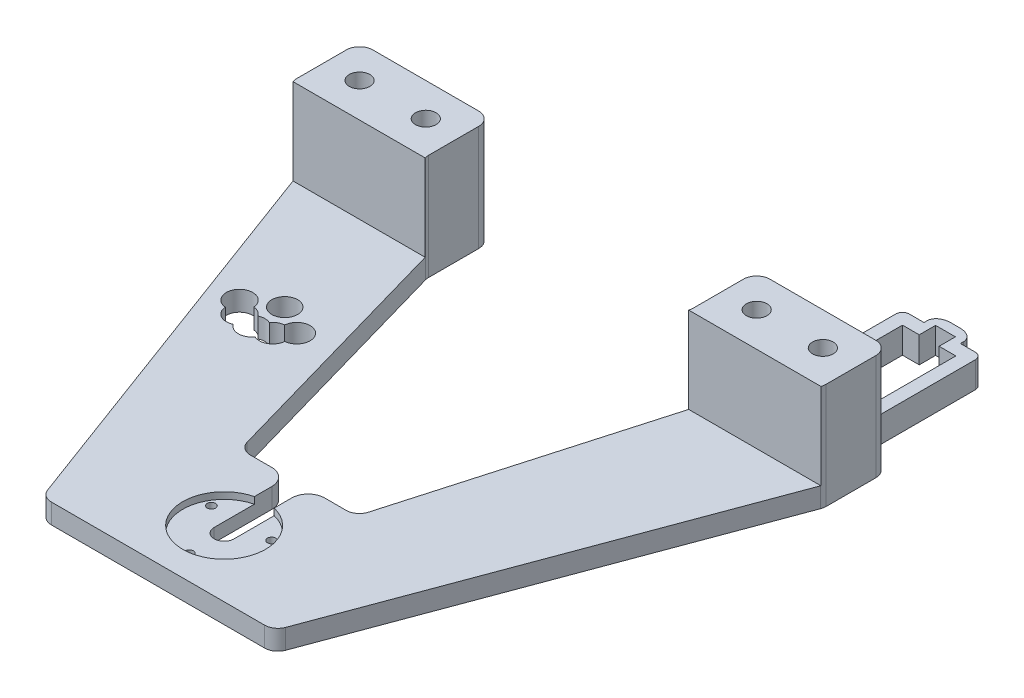
SolidWorks part; units mm, degrees
ref_plane "Front Plane" through (0, 0, 0) normal (0, 0, 1) x (1, 0, 0)
ref_plane "Top Plane" through (0, 0, 0) normal (0, 1, 0) x (1, 0, 0)
ref_plane "Right Plane" through (0, 0, 0) normal (1, 0, 0) x (0, 0, -1)
sketch "Sketch1" plane through (0, 0, 0) normal (0, 1, 0) x (1, 0, 0)
  line L0 (-96.52, 178.9428) -> (-55.88, 178.9428)
  line L1 (-50.8, 173.8628) -> (-50.8, 154.6109)
  line L3 (-101.6, 154.8128) -> (-101.6, 173.8628)
  line L4 (0, 53.8) -> (-18.3922, 53.8)
  line L6 (-40.9175, 0) -> (0, 0)
  line L8 (-101.2823, 153.0443) -> (-45.6797, 3.3116)
  line L9 (0, 53.8) -> (0, 0)
  line L10 (-23.2771, 57.4855) -> (-50.6049, 153.2164)
  circle A0 centre (-88.9, 166.2428) radius 3.9687
  circle A1 centre (-63.5, 166.2428) radius 3.9688
  arc A2 (-55.88, 178.9428) -> (-50.8, 173.8628) centre (-55.88, 173.8628) cw
  arc A3 (-96.52, 178.9428) -> (-101.6, 173.8628) centre (-96.52, 173.8628) ccw
  arc A4 (-101.2823, 153.0443) -> (-101.6, 154.8128) centre (-96.52, 154.8128) cw
  arc A5 (-45.6797, 3.3116) -> (-40.9175, 0) centre (-40.9175, 5.08) ccw
  arc A6 (-18.3922, 53.8) -> (-23.2771, 57.4855) centre (-18.3922, 58.88) cw
  arc A7 (-50.8, 154.6109) -> (-50.6049, 153.2164) centre (-45.72, 154.6109) ccw
  point P18 (-50.8, 178.9428)
  point P21 (-101.6, 178.9428)
  point P47 (0, 26.9)
  point P51 (-101.6, 153.9)
  point P54 (-44.45, 0)
  point P57 (-22.225, 53.8)
  point P60 (-50.8, 153.9)
  dimension "D3" = 7.9375
  dimension "D6" = 5.08
  dimension "D13" = 5.08
  dimension "D14" = 5.08
  dimension "D15" = 5.08
  dimension "D16" = 5.08
  dimension "D1" = 50.8
  dimension "D2" = 19.05
  dimension "D4" = 12.7
  dimension "D5" = 12.7
  dimension "D7" = 101.6
  dimension "D8" = 127
  dimension "D9" = 12.7
  dimension "D10" = 44.45
  dimension "D11" = 22.225
  dimension "D12" = 53.8
extrude "Boss-Extrude2" add sketch "Sketch1" along normal blind 40.64
mirror "Mirror1" about plane through (0, 40.64, -53.8) normal (-1, 0, 0) of "Boss-Extrude2"
sketch "Sketch4" plane through (0, 40.64, 0) normal (0, 1, 0) x (1, 0, 0)
  line L2 (18.3922, 53.8) -> (-18.3922, 53.8) construction
  circle A0 centre (11.5484, 32.0195) radius 1.5875
  circle A1 centre (0, 12.017) radius 1.5875
  circle A2 centre (-11.5484, 32.0195) radius 1.5875
  point P9 (0, 25.352)
  dimension "D1" = 3.175
  dimension "D3" = 28.448
  dimension "D4" = 13.335
  dimension "D2" = 3
extrude "Cut-Extrude1" cut sketch "Sketch4" against normal through all
sketch "Sketch5" plane through (0, 0, 0) normal (0, 1, 0) x (1, 0, 0)
  line L0 (18.3922, 53.8) -> (-18.3922, 53.8) construction
  circle A0 centre (0, 25.352) radius 15.875
  dimension "D2" = 31.75
  dimension "D1" = 28.448
extrude "Cut-Extrude2" cut sketch "Sketch5" along normal blind 5.08 from offset 5.08
sketch "Sketch7" plane through (0, 40.64, 0) normal (0, 1, 0) x (1, 0, 0)
  line L1 (-155.1296, 153.0819) -> (166.308, 153.0819)
  line L2 (-155.1296, 153.0819) -> (-155.1296, 0)
  line L3 (-155.1296, 0) -> (166.308, 0)
  line L4 (166.308, 153.0819) -> (166.308, 0)
  line L5 (-40.9175, 0) -> (40.9175, 0) construction
extrude "Cut-Extrude3" cut sketch "Sketch7" against normal offset from surface (33.02 mm away) 33.02 up to face at (11.5484, 40.64, -30.432)
sketch "Sketch8" plane through (0, 0, 0) normal (0, 1, 0) x (1, 0, 0)
  line L0 (0, 25.352) -> (0, 53.8) construction
  line L1 (18.3922, 53.8) -> (-18.3922, 53.8) construction
  line L2 (-3.81, 25.352) -> (-3.81, 53.8)
  line L3 (3.81, 25.352) -> (3.81, 53.8)
  arc A0 (-3.81, 25.352) -> (3.81, 25.352) centre (0, 25.352) ccw
  arc A1 (3.81, 53.8) -> (-3.81, 53.8) centre (0, 53.8) ccw
  point P5 (0, 39.576)
  dimension "D1" = 7.62
extrude "Cut-Extrude5" cut sketch "Sketch8" along direction (0, 1, 0) on the side of the normal through all
fillet "Fillet1" radius 6.35 1 edges at (-3.81, 3.81, -53.8) type face fillet first side face at (-11.1011, 3.81, -53.8) second side face at (-3.81, 4.2333, -39.9717)
fillet "Fillet2" radius 6.35 1 edges at (3.81, 3.81, -53.8) type face fillet first side face at (11.1011, 3.81, -53.8) second side face at (3.81, 4.2333, -39.9717)
sketch "Sketch9" plane through (0, 0, 0) normal (0, 1, 0) x (1, 0, 0)
  line L0 (-63.5, 166.2428) -> (-63.5, 178.9428) construction
  line L2 (-88.9, 166.2428) -> (-88.9, 178.9428) construction
  line L3 (-88.9, 166.2428) -> (-63.5, 166.2428) construction
  line L4 (-91.44, 173.9428) -> (-91.44, 224.7428)
  line L5 (-91.44, 224.7428) -> (-60.96, 224.7428)
  line L6 (-60.96, 224.7428) -> (-60.96, 173.9428)
  line L7 (-60.96, 173.9428) -> (-91.44, 173.9428)
  line L8 (-55.88, 178.9428) -> (-96.52, 178.9428) construction
  point P13 (-76.2, 173.9428)
  point P14 (-76.2, 166.2428)
  dimension "D1" = 30.48
  dimension "D2" = 50.8
  dimension "D3" = 5
extrude "Extrude-Thin1" add sketch "Sketch9" along normal blind 10 thin thin type one direction reverse wall 5
sketch "Sketch14" plane through (0, 0, 0) normal (0, -1, 0) x (1, 0, 0)
  line L0 (-65.96, -178.9428) -> (-86.44, -178.9428) construction
  line L1 (-81.2, -174.9428) -> (-71.2, -174.9428) construction
  line L2 (-76.2, -178.9428) -> (-76.2, -173.6531) construction
  circle A0 centre (-81.2, -174.9428) radius 1.95
  circle A1 centre (-71.2, -174.9428) radius 1.95
  point P6 (-76.2, -174.9428)
  dimension "D1" = 3.9
  dimension "D4" = 3.9
  dimension "D2" = 4
  dimension "D3" = 10
extrude "Cut-Extrude6" cut sketch "Sketch14" against normal blind 20
ref_plane "Plane2" through (-60.96, 10, -178.9428) normal (-1, 0, 0) x (0, 0, 1)
ref_plane "Plane3" through (-76.2, 0, 0) normal (1, 0, 0) x (0, 0, -1)
sketch "Sketch18" plane through (-60.96, 10, -178.9428) normal (-1, 0, 0) x (0, 0, 1)
  line L0 (-1.27, 0) -> (0, 1.524)
  line L1 (-45.8, 0) -> (0, 0) construction
  line L2 (0, 30.64) -> (0, -10) construction
  line L3 (0, 1.524) -> (0, 0)
  line L4 (0, 0) -> (-1.27, 0)
  dimension "D1" = 1.524
  dimension "D2" = 1.27
extrude "Boss-Extrude4" add sketch "Sketch18" along normal up to vertex (5 mm away) up to point (-65.96, 10, -178.9428)
mirror "Mirror3" about plane through (-76.2, 0, 0) normal (1, 0, 0) of "Boss-Extrude4"
mirror "Mirror5" about plane through (0, 0, 0) normal (1, 0, 0) of "Mirror3", "Boss-Extrude4", "Cut-Extrude6", "Extrude-Thin1"
fillet "Fillet3" radius 2.54 4 edges at (-91.44, 5, -224.7428) (-60.96, 5, -224.7428) (60.96, 5, -224.7428) (91.44, 5, -224.7428)
sketch "Sketch19" plane through (0, 0, -224.7428) normal (0, 0, -1) x (-1, 0, 0)
  line L1 (72.39, 10) -> (80.01, 10)
  line L2 (72.39, 10) -> (72.39, -0.16)
  line L3 (72.39, -0.16) -> (80.01, -0.16)
  line L4 (80.01, 10) -> (80.01, -0.16)
  line L9 (63.5, 10) -> (88.9, 10) construction
  line L10 (76.2, 38.5994) -> (76.2, -38.5994) construction
  point P6 (76.2, 10)
  dimension "D1" = 7.62
  dimension "D2" = 10.16
sketch "Sketch20" plane through (0, 0, 0) normal (0, 1, 0) x (1, 0, 0)
  line L0 (-63.5, 224.7428) -> (-88.9, 224.7428) construction
  line L1 (-83.185, 224.7428) -> (-69.215, 224.7428)
  line L2 (-83.185, 224.7428) -> (-83.185, 229.8228)
  line L3 (-83.185, 229.8228) -> (-69.215, 229.8228)
  line L4 (-69.215, 224.7428) -> (-69.215, 229.8228)
  line L5 (-76.2, -38.5994) -> (-76.2, 38.5994) construction
  dimension "D1" = 13.97
  dimension "D2" = 5.08
  dimension "D3" = 6.985
extrude "Boss-Extrude5" add sketch "Sketch20" along normal up to vertex (10 mm away) up to point (-88.9, 10, -224.7428)
fillet "Fillet7" radius 3.81 1 edges at (-83.185, 5, -229.8228) second distance 5.08 first distance on face at (-83.185, 5, -227.2828)
fillet "Fillet6" radius 3.81 1 edges at (-69.215, 5, -229.8228) second distance 5.08 first distance on face at (-69.215, 5, -227.2828)
extrude "Cut-Extrude10" cut sketch "Sketch19" against normal up to surface (5 mm away) and the other way blind 1.27 up to face at (-76.2, 5, -219.7428)
mirror "Mirror6" about plane through (0, 0, 0) normal (1, 0, 0) of "Cut-Extrude6", "Cut-Extrude10", "Fillet6", "Fillet7", "Boss-Extrude5"
sketch "Sketch21" plane through (0, 0, -178.9428) normal (0, 0, -1) x (-1, 0, 0)
  line L1 (40.2088, 57.3257) -> (117.296, 57.3257)
  line L2 (40.2088, 57.3257) -> (40.2088, -11.7482)
  line L3 (40.2088, -11.7482) -> (117.296, -11.7482)
  line L4 (117.296, 57.3257) -> (117.296, -11.7482)
extrude "Cut-Extrude11" cut sketch "Sketch21" along normal through all
sketch "Sketch22" plane through (0, 0, 0) normal (0, -1, 0) x (1, 0, 0)
  line L0 (-60.96, -123.9428) -> (-60.96, -233.9428) construction
  circle A0 centre (-60.96, -109.5725) radius 4.953
  dimension "D1" = 9.906
sketch "Sketch23" plane through (0, 0, 0) normal (0, -1, 0) x (1, 0, 0)
  line L0 (-60.96, -123.9428) -> (-60.96, -233.9428) construction
  line L1 (-60.96, -109.5725) -> (-60.96, -96.8725) construction
  line L2 (-60.96, -109.5725) -> (-60.96, -96.8725) construction
  circle A1 centre (-67.31, -98.5739) radius 5.08
  circle A13 centre (-60.96, -96.8725) radius 5.08
  circle A15 centre (-71.9585, -103.2225) radius 5.08
  circle A16 centre (-54.61, -98.5739) radius 5.08
  circle A17 centre (-49.9615, -103.2225) radius 5.08
  point P10 (0, 0)
  dimension "D1" = 10.16
  dimension "D3" = 3
  dimension "D4" = 12.7
  dimension "D6" = 12.7
  dimension "D5" = 3
extrude "Cut-Extrude12" cut sketch "Sketch23" against normal through all contours A1 A15 | A1 A15 | A15 A1 A13 | A1 A13 | A16 A13 A1 | A13 A16 | A17 A16 A13 | A16 A17 | A16 A17 region at (-64.135, 0, -97.7232) region at (-60.96, 0, -96.1) region at (-67.6962, 0, -97.905) region at (-69.6343, 0, -100.8982) region at (-72.6842, 0, -103.9481) region at (-54.2238, 0, -97.905) region at (-57.785, 0, -97.7232) region at (-49.2358, 0, -103.9481) region at (-52.2857, 0, -100.8982)
extrude "Cut-Extrude13" cut sketch "Sketch22" against normal through all
